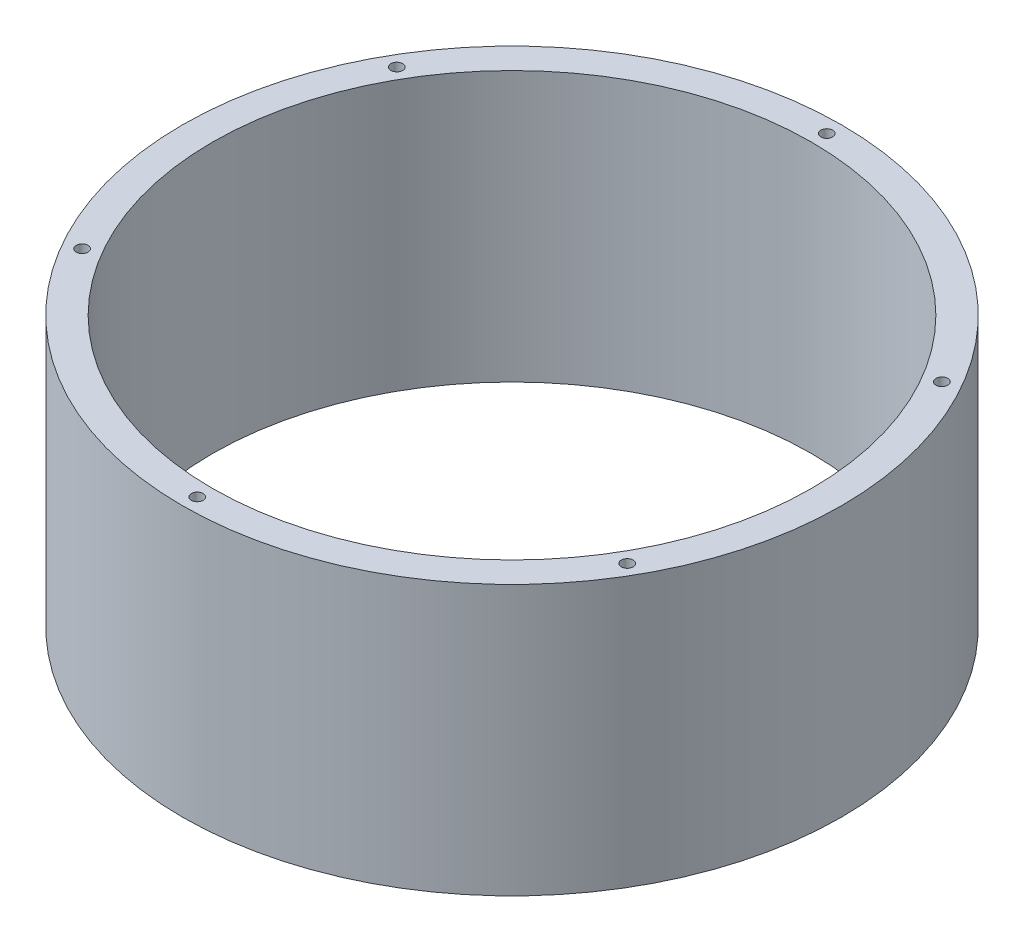
SolidWorks part; units mm, degrees
ref_plane "Front" through (0, 0, 0) normal (0, 0, 1) x (1, 0, 0)
ref_plane "Top" through (0, 0, 0) normal (0, 1, 0) x (1, 0, 0)
ref_plane "Right" through (0, 0, 0) normal (1, 0, 0) x (0, 0, -1)
sketch "Sketch1" plane through (0, 0, 0) normal (0, 1, 0) x (1, 0, 0)
  circle A0 centre (0, 0) radius 63.5
  circle A1 centre (0, 0) radius 69.85
  dimension "D1" = 139.7
  dimension "D2" = 127
extrude "Extrude1" add sketch "Sketch1" along normal blind 57.15
hole_wizard "#3-56 Tapped Hole1" positions "3DSketch4" profile "Sketch5" tap size "#3-56" standard "Ansi Inch"
sketch3d "3DSketch4"
  point P8 (0, 0, 66.675)
  dimension "D5" = 66.675
sketch "Sketch5" plane through (0, 0, 66.675) normal (1, 0, 0) x (0, 0, -1)
  line L0 (0, 0) -> (0, 6.9757)
  line L1 (0, 6.9757) -> (1.0414, 6.35)
  line L2 (1.0414, 6.35) -> (1.0414, 5.08)
  line L3 (1.0414, 5.08) -> (1.2573, 5.08)
  line L4 (1.2573, 5.08) -> (1.2573, 0)
  line L5 (1.2573, 0) -> (0, 0)
  line L10 (0, 6.9757) -> (-1.0414, 6.35) construction
  line L11 (0, -6.35) -> (0, 107.95) construction
  dimension "Tap Drill Dia." = 2.0828
  dimension "Tap Drill Depth" = 6.35
  dimension "Thread Major Dia." = 2.5146
  dimension "Thread Depth" = 5.08
  dimension "Drill Angle" = 118
ref_axis "Axis1" through (0, 65.1967, 0) along (0, -1, 0)
pattern_circular "CirPattern1" count 6 over 360 about axis through (0, 65.1967, 0) along (0, -1, 0) of "#3-56 Tapped Hole1"
hole_wizard "#3-56 Tapped Hole2" positions "3DSketch5" profile "Sketch6" tap size "#3-56" standard "Ansi Inch"
sketch3d "3DSketch5"
  line L0 (0, 65.1967, 0) -> (0, 0, 0) construction
  point P0 (0.0056, 57.15, -66.675)
  dimension "D1" = 66.675
sketch "Sketch6" plane through (0.0056, 57.15, -66.675) normal (1, 0, 0) x (0, 0, 1)
  line L0 (0, 0) -> (0, 7.0265)
  line L1 (0, 7.0265) -> (1.0414, 6.4008)
  line L2 (1.0414, 6.4008) -> (1.0414, 5.0292)
  line L3 (1.0414, 5.0292) -> (1.2573, 5.0292)
  line L4 (1.2573, 5.0292) -> (1.2573, 0)
  line L5 (1.2573, 0) -> (0, 0)
  line L10 (0, 7.0265) -> (-1.0414, 6.4008) construction
  line L11 (0, -6.35) -> (0, 107.95) construction
  dimension "Tap Drill Dia." = 2.0828
  dimension "Tap Drill Depth" = 6.4008
  dimension "Thread Major Dia." = 2.5146
  dimension "Thread Depth" = 5.0292
  dimension "Drill Angle" = 118
pattern_circular "CirPattern2" count 6 over 360 about axis through (0, 65.1967, 0) along (0, -1, 0) of "#3-56 Tapped Hole2"
